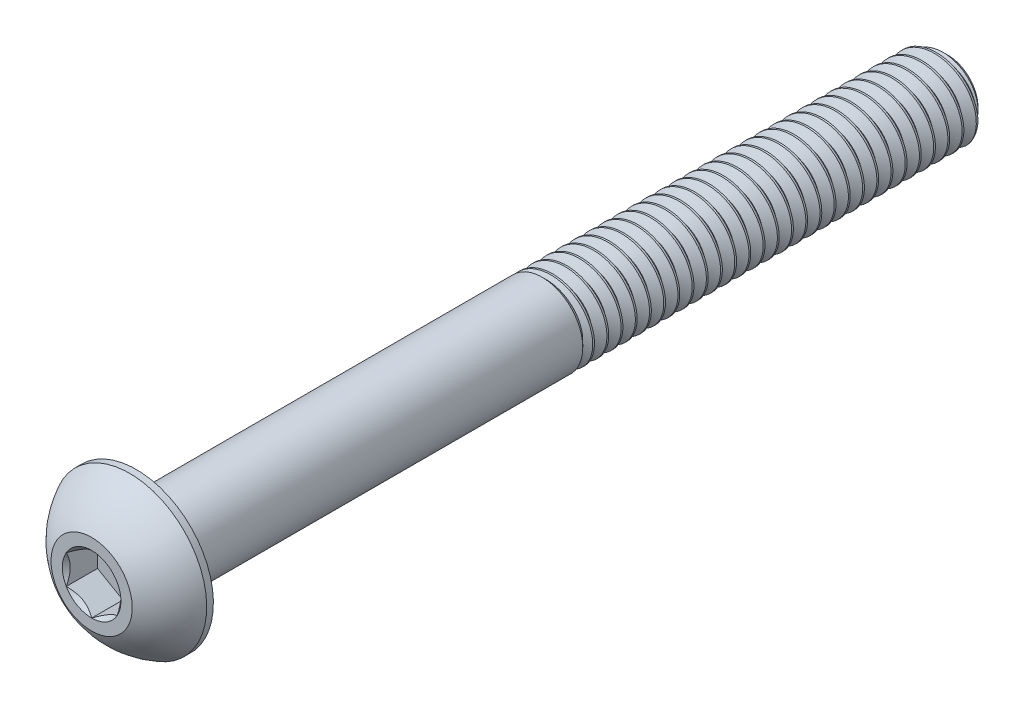
SolidWorks part; units mm, degrees
ref_plane "Front" through (0, 0, 0) normal (0, 0, 1) x (1, 0, 0)
ref_plane "Top" through (0, 0, 0) normal (0, 1, 0) x (1, 0, 0)
ref_plane "Right" through (0, 0, 0) normal (1, 0, 0) x (0, 0, -1)
sketch "Sketch1" plane through (0, 0, 0) normal (1, 0, 0) x (0, 0, -1)
  line L2 (-20, 2) -> (20, 2)
  line L3 (20, 2) -> (20, 0)
  line L4 (20, 0) -> (-20, 0)
  line L6 (-20.33, 3.8) -> (-20, 3.8) construction
  line L7 (20, 2) -> (20, -2) construction
  line L8 (-22.2, 0) -> (-20, 0) construction
  line L9 (-20, 3.8) -> (-20, -3.8) construction
  line L11 (-20, 2) -> (-20, 0)
  line L13 (-22.2, 1.25) -> (-22.2, -1.25) construction
  line L14 (-22.2, 1.25) -> (-22.2, 2) construction
  line L15 (19.9563, 2.0758) -> (20.3063, 1.4696) construction
  line L16 (20.3063, 1.4696) -> (20.6563, 2.0758) construction
  line L17 (20.6563, 2.0758) -> (19.9563, 2.0758) construction
  line L18 (20, 2) -> (20.6125, 2) construction
  line L19 (20.3063, 2.0758) -> (20.3063, 2) construction
  line L20 (20.3063, 2) -> (20.3063, 1.5453) construction
  line L21 (20.3063, 1.5453) -> (20.3063, 1.4696) construction
  line L22 (20.2625, 1.5453) -> (20.35, 1.5453)
  line L23 (19.9781, 2.0379) -> (20.6344, 2.0379)
  line L24 (20.35, 1.5453) -> (20.6344, 2.0379)
  line L25 (20.2625, 1.5453) -> (19.9781, 2.0379)
  line L26 (19.475, 2) -> (20, 1.475)
  arc A3 (-22.2, 2) -> (-20.33, 3.8) centre (-18.4736, 0) cw construction
  point P29 (20.3063, 2.0379)
  point P30 (18.25, -2)
  point P32 (0, 2)
  point P33 (-5, 0)
  point P34 (0, 0)
  point P35 (-15, 0)
  dimension "Thread Size" = 4
  dimension "D1" = 0.33
  dimension "Head Height" = 2.2
  dimension "Head Diameter" = 7.6
  dimension "Length" = 40
  dimension "Drive Size" = 2.5
  dimension "Thread Pitch" = 0.7
  dimension "D3" = 0.0875
  dimension "D2" = 0.525
  dimension "D4" = 45
  dimension "D5" = 1.75
  dimension "Minimum Thread Length" = 20
  dimension "D6" = 5
  dimension "D7" = 5
sketch "Sketch10" plane through (0, 0, 0) normal (1, 0, 0) x (0, 0, -1)
  line L0 (19.475, 2) -> (20, 1.475) construction
  line L1 (19.475, 2) -> (20, 1.475)
  line L4 (20, 2) -> (-20, 2)
  line L5 (20, 0) -> (20, 2)
  line L6 (-20, 0) -> (20, 0)
  line L7 (-20, 2) -> (-20, 0)
  line L8 (19.475, 2) -> (-20, 2)
  line L9 (20, 0) -> (20, 1.475)
  line L10 (-20, 0) -> (20, 0)
  line L11 (-20, 2) -> (-20, 0)
  dimension "D1" = 0
revolve "Revolve3" add sketch "Sketch10" angle 360 about L8
sketch "Sketch7" plane through (0, 0, 0) normal (1, 0, 0) x (0, 0, -1)
  line L6 (-20.33, 3.8) -> (-20, 3.8) construction
  line L8 (-22.2, 0) -> (-20, 0) construction
  line L11 (-20, 3.8) -> (-20, -3.8) construction
  line L12 (-20.33, 3.8) -> (-20, 3.8)
  line L13 (-22.2, 0) -> (-20, 0)
  line L14 (-22.2, 1.25) -> (-22.2, -1.25) construction
  line L15 (-20, 3.8) -> (-20, 0)
  line L16 (-22.2, 2) -> (-22.2, 0)
  arc A2 (-20.33, 3.8) -> (-22.2, 2) centre (-18.4736, 0) ccw construction
  arc A3 (-20.33, 3.8) -> (-22.2, 2) centre (-18.4736, 0) ccw
revolve "Revolve2" add sketch "Sketch7" angle 360 mid plane about L13
sketch "Sketch5" plane through (0, 0, 22.2) normal (0, 0, 1) x (1, 0, 0)
  line L1 (1.25, -0.7217) -> (1.25, 0.7217)
  line L2 (1.25, 0.7217) -> (0, 1.4434)
  line L3 (0, 1.4434) -> (-1.25, 0.7217)
  line L4 (-1.25, 0.7217) -> (-1.25, -0.7217)
  line L5 (-1.25, -0.7217) -> (0, -1.4434)
  line L6 (0, -1.4434) -> (1.25, -0.7217)
  circle A0 centre (0, 0) radius 1.25 construction
extrude "Cut-Extrude2" cut sketch "Sketch5" against normal blind 1.54
sketch "Sketch6" plane through (0, 0, 22.2) normal (0, 0, 1) x (1, 0, 0)
  circle A0 centre (0, 0) radius 1.4434
extrude "Cut-Extrude3" cut sketch "Sketch6" against normal blind 1.54 draft 45
ref_plane "Plane1" through (0, 0, 0) normal (0, 0, 1) x (1, 0, 0)
sketch "Sketch9" plane through (0, 0, 0) normal (0, 0, -1) x (-1, 0, 0)
  circle A0 centre (0, 0) radius 2 construction
  circle A4 centre (0, 0) radius 2
split "Split1" trim tools "Plane1" bodies to split 113 resulting bodies 123 124
sketch "Sketch11" plane through (0, 0, -20) normal (0, 0, -1) x (-1, 0, 0)
  circle A0 centre (0, 0) radius 2 construction
  circle A1 centre (0, 0) radius 2
curve "Helix/Spiral1" pitch 0.7 height 22.2 turns 31.7143
sketch "Sketch12" plane through (0, 0, 0) normal (1, 0, 0) x (0, 0, -1)
  line L0 (20.2625, 1.5453) -> (20.35, 1.5453) construction
  line L1 (20.35, 1.5453) -> (20.6344, 2.0379) construction
  line L2 (19.9781, 2.0379) -> (20.6344, 2.0379) construction
  line L3 (20.2625, 1.5453) -> (19.9781, 2.0379) construction
  line L4 (20.2625, 1.5453) -> (20.35, 1.5453)
  line L5 (20.35, 1.5453) -> (20.6344, 2.0379)
  line L6 (19.9781, 2.0379) -> (20.6344, 2.0379)
  line L7 (20.2625, 1.5453) -> (19.9781, 2.0379)
sweep "Cut-Sweep2" cut profiles "Sketch12" path "Helix/Spiral1" align with end faces yes
extrude "Boss-Extrude1" add sketch "Sketch9" along normal blind 10 draft 45
equation "\"D1@Cut-Extrude2\" = \"Head Height@Sketch1\" * .7"
equation "\"D1@Sketch1\" = \"Head Height@Sketch1\" * .15"
equation "\"D1@Cut-Extrude3\" = \"D1@Cut-Extrude2\""
equation "\"D3@Sketch1\" = \"Thread Pitch@Sketch1\" / 8"
equation "\"D2@Sketch1\" = \"Thread Pitch@Sketch1\" * 0.75"
equation "\"D3@Helix/Spiral1\"=\"Minimum Thread Length@Sketch1\" + \"Head Height@Sketch1\""
equation "\"D4@Helix/Spiral1\" = \"Thread Pitch@Sketch1\""
equation "\"D5@Sketch1\" = \"Thread Pitch@Sketch1\" * 2.5"
